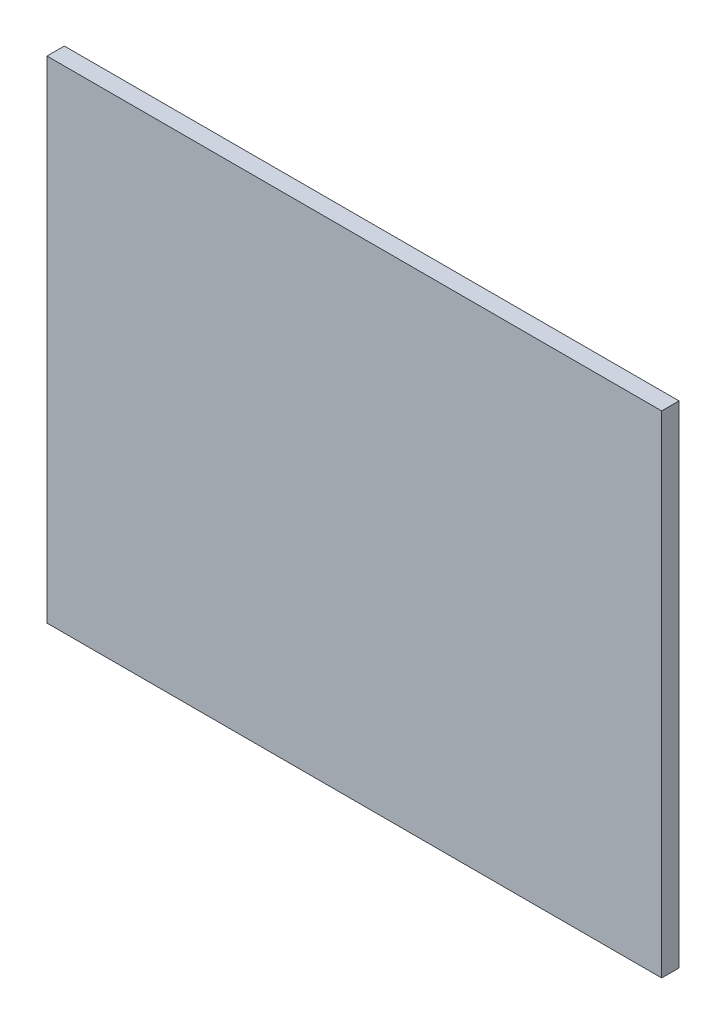
SolidWorks part; units mm, degrees
ref_plane "Front Plane" through (0, 0, 0) normal (0, 0, 1) x (1, 0, 0)
ref_plane "Top Plane" through (0, 0, 0) normal (0, 1, 0) x (1, 0, 0)
ref_plane "Right Plane" through (0, 0, 0) normal (1, 0, 0) x (0, 0, -1)
sketch "Sketch1" plane through (0, 0, 0) normal (0, 0, 1) x (1, 0, 0)
  line L1 (-56.325, -45) -> (56.325, -45)
  line L2 (-56.325, -45) -> (-56.325, 45)
  line L3 (-56.325, 45) -> (56.325, 45)
  line L4 (56.325, -45) -> (56.325, 45)
  line L5 (-56.325, -45) -> (56.325, 45) construction
  line L6 (-56.325, 45) -> (56.325, -45) construction
  point P0 (0, 0)
  dimension "D1" = 112.65
  dimension "D2" = 90
extrude "Boss-Extrude1" add sketch "Sketch1" along normal blind 3.175
